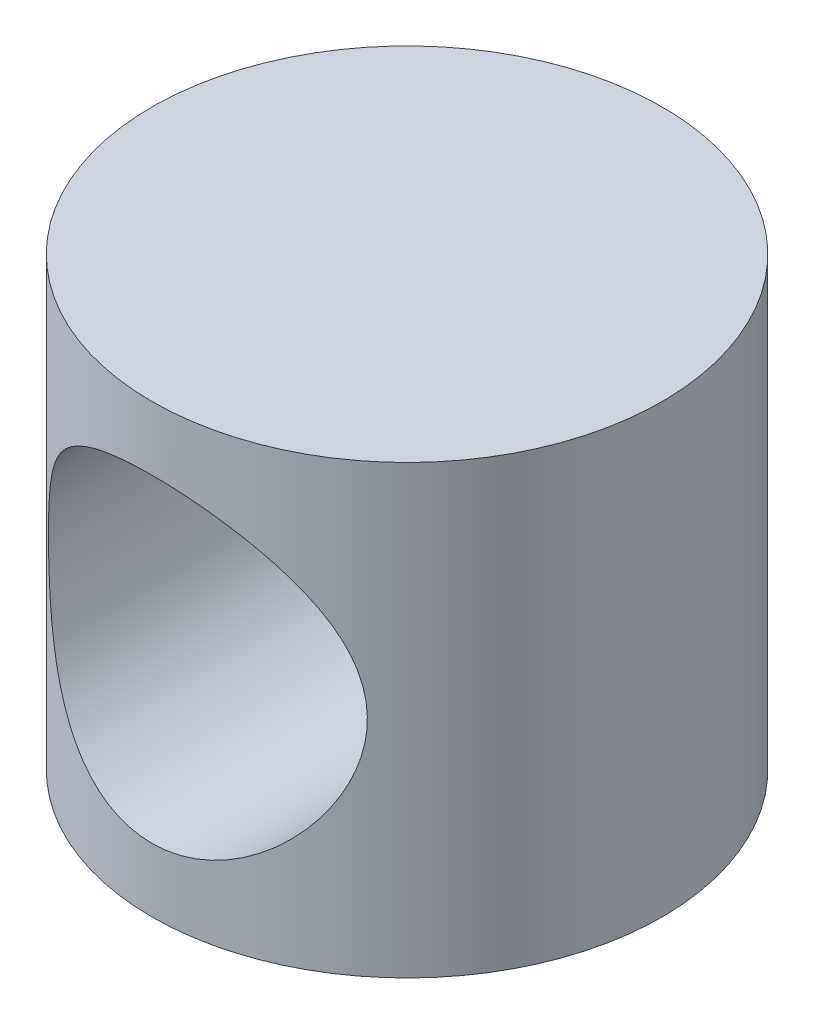
SolidWorks part; units mm, degrees
ref_plane "Спереди" through (0, 0, 0) normal (0, 0, 1) x (1, 0, 0)
ref_plane "Сверху" through (0, 0, 0) normal (0, 1, 0) x (1, 0, 0)
ref_plane "Справа" through (0, 0, 0) normal (1, 0, 0) x (0, 0, -1)
other "Configuration Table"
sketch "Sketch1" plane through (0, 0, 0) normal (0, 1, 0) x (1, 0, 0)
  circle A0 centre (0, 0) radius 4
  dimension "D1" = 8
extrude "Boss-Extrude1" add sketch "Sketch1" along normal blind 7
sketch "Sketch2" plane through (0, 0, 0) normal (0, 0, 1) x (1, 0, 0)
  line L0 (4, 7) -> (-4, 7) construction
  circle A0 centre (0, 3.5) radius 2.5
  dimension "D1" = 3.5
  dimension "D2" = 5
extrude "Cut-Extrude1" cut sketch "Sketch2" against normal blind 7 and the other way blind 7
